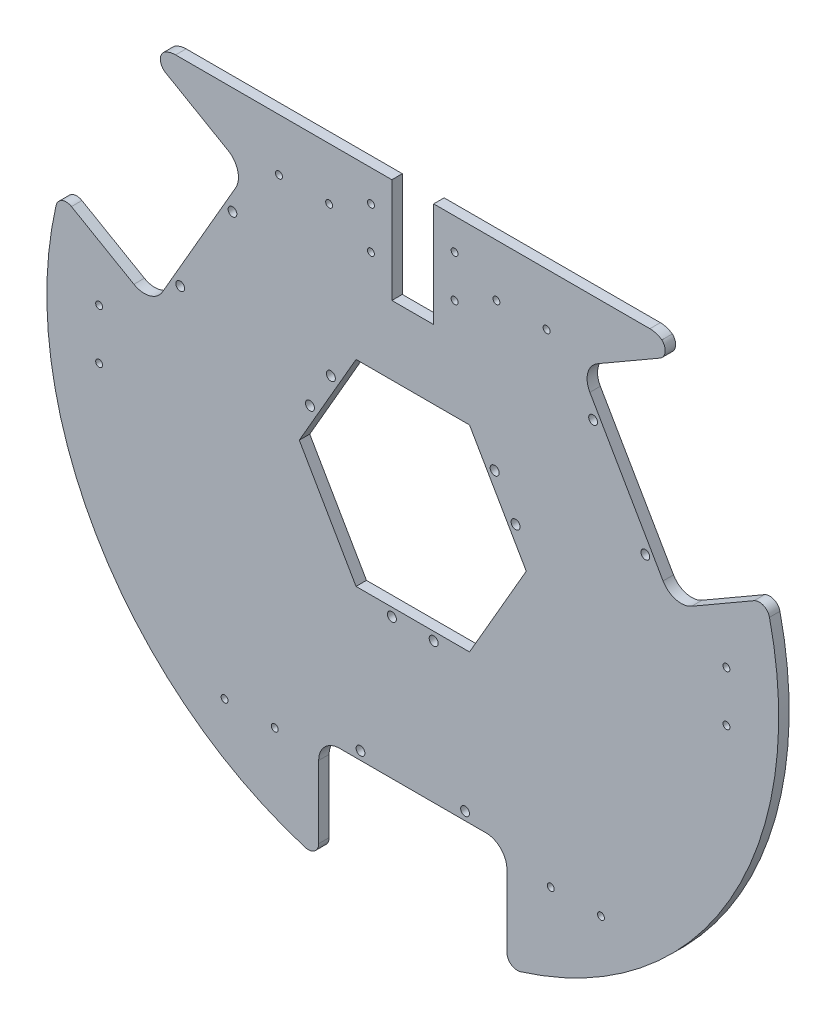
SolidWorks part; units mm, degrees
material "AISI 304"
ref_plane "前基準面" through (0, 0, 0) normal (0, 0, 1) x (1, 0, 0)
ref_plane "上基準面" through (0, 0, 0) normal (0, 1, 0) x (1, 0, 0)
ref_plane "右基準面" through (0, 0, 0) normal (1, 0, 0) x (0, 0, -1)
ref_axis "基準軸1" through (0, 0, -0.25) along (0, 0, 1)
sketch "草圖1" plane through (0, 0, 0) normal (0, 0, 1) x (1, 0, 0)
  circle A1 centre (0, 0) radius 175
  dimension "D1" = 350
extrude "填料-伸長1" add sketch "草圖1" along normal blind 5
sketch "草圖6" plane through (0, 0, 5) normal (0, 0, 1) x (1, 0, 0)
  line L10 (0, 0) -> (0, -143.5577) construction
  line L13 (-45, -169.1153) -> (-45, -118)
  line L14 (-45, -118) -> (45, -118)
  line L15 (45, -169.1153) -> (45, -118)
  line L16 (-45, -169.1153) -> (45, -118) construction
  line L17 (-45, -118) -> (45, -169.1153) construction
  arc A0 (-45, -169.1153) -> (45, -169.1153) centre (0, 0) ccw
  circle A1 centre (0, 0) radius 175 construction
  dimension "D1" = 118
  dimension "D2" = 90
extrude "除料-伸長1" cut sketch "草圖6" against normal through all
sketch "草圖12" plane through (0, 0, 5) normal (0, 0, 1) x (1, 0, 0)
  line L0 (-117.1537, 130) -> (117.1537, 130)
  arc A0 (45, -169.1153) -> (-45, -169.1153) centre (0, 0) ccw construction
  arc A1 (-117.1537, 130) -> (117.1537, 130) centre (0, 0) cw
  arc A2 (45, -169.1153) -> (-45, -169.1153) centre (0, 0) ccw construction
  dimension "D1" = 130
extrude "除料-伸長3" cut sketch "草圖12" against normal through all
hole_wizard "M5x0.8 螺紋孔1" positions "草圖4" profile "草圖5" tap size "M5x0.8" standard "Ansi Metric" end condition through all
sketch "草圖4" plane through (0, 0, 5) normal (0, 0, 1) x (1, 0, 0)
  line L0 (0, -118) -> (0, -114) construction
  line L4 (-25, -114) -> (25, -114) construction
  line L6 (45, -118) -> (-45, -118) construction
  point P10 (-25, -114)
  point P11 (25, -114)
  dimension "D1" = 4
  dimension "D2" = 50
sketch "草圖5" plane through (25, -114, 5) normal (1, 0, 0) x (0, -1, 0)
  line L0 (0, 0) -> (0, 5)
  line L1 (0, 5) -> (2.1, 5)
  line L2 (2.1, 5) -> (2.1, 0)
  line L5 (2.1, 0) -> (0, 0)
  line L11 (0, -6.35) -> (0, 107.95) construction
  dimension "貫穿螺孔鑽直徑" = 4.2
  dimension "貫穿螺孔鑽深度" = 5
hole_wizard "M4 餘隙孔1" positions "草圖9" profile "草圖10" hole size "M4" standard "Ansi Metric" end condition through all
sketch "草圖9" plane through (0, 0, 5) normal (0, 0, 1) x (1, 0, 0)
  line L0 (-25, -114) -> (25, -114) construction
  line L3 (0, -114) -> (0, -51) construction
  line L6 (-10, -51) -> (10, -51) construction
  point P14 (-10, -51)
  point P15 (10, -51)
  dimension "D1" = 20
  dimension "D2" = 63
sketch "草圖10" plane through (10, -51, 5) normal (1, 0, 0) x (0, -1, 0)
  line L0 (0, 0) -> (0, 5)
  line L1 (0, 5) -> (2.15, 5)
  line L2 (2.15, 5) -> (2.15, 0)
  line L5 (2.15, 0) -> (0, 0)
  line L11 (0, -6.35) -> (0, 107.95) construction
  dimension "貫穿孔直徑" = 4.3
  dimension "貫穿孔深度" = 5
fillet "圓角1" radius 10 2 edges at (-45, -118, 2.5) (45, -118, 2.5)
fillet "圓角2" radius 5 2 edges at (45, -169.1153, 2.5) (-45, -169.1153, 2.5)
pattern_circular "環狀複製排列1" count 3 over 360 about axis through (0, 0, -0.25) along (0, 0, 1) of "M5x0.8 螺紋孔1", "除料-伸長1", "M4 餘隙孔1", "圓角1", "圓角2"
sketch "草圖11" plane through (0, 0, 5) normal (0, 0, 1) x (1, 0, 0)
  line L7 (54.2709, 0) -> (27.1355, 47)
  line L8 (27.1355, 47) -> (-27.1355, 47)
  line L9 (-27.1355, 47) -> (-54.2709, 0)
  line L10 (-54.2709, 0) -> (-27.1355, -47)
  line L11 (-27.1355, -47) -> (27.1355, -47)
  line L12 (27.1355, -47) -> (54.2709, 0)
  circle A1 centre (0, 0) radius 47 construction
  dimension "D1" = 94
extrude "除料-伸長2" cut sketch "草圖11" against normal through all
hole_wizard "M4x0.7 螺紋孔1" positions "草圖17" profile "草圖18" tap size "M4x0.7" standard "Ansi Metric" end condition through all
sketch "草圖17" plane through (0, 0, 0) normal (0, 0, 1) x (1, 0, 0)
  line L0 (0, 0) -> (0, 130) construction
  line L1 (-117.1537, 130) -> (117.1537, 130) construction
  line L2 (-40, 105) -> (-64, 105) construction
  line L5 (40, 105) -> (64, 105) construction
  point P7 (-40, 105)
  point P10 (40, 105)
  point P13 (-64, 105)
  point P18 (64, 105)
  dimension "D1" = 40
  dimension "D2" = 105
  dimension "D3" = 24
sketch "草圖18" plane through (64, 105, 0) normal (1, 0, 0) x (0, 1, 0)
  line L0 (0, 0) -> (0, 5)
  line L1 (0, 5) -> (1.65, 5)
  line L2 (1.65, 5) -> (1.65, 0)
  line L5 (1.65, 0) -> (0, 0)
  line L11 (0, -6.35) -> (0, 107.95) construction
  dimension "貫穿螺孔鑽直徑" = 3.3
  dimension "貫穿螺孔鑽深度" = 5
hole_wizard "M4x0.7 螺紋孔2" positions "草圖21" profile "草圖22" tap size "M4x0.7" standard "Ansi Metric" end condition through all
sketch "草圖21" plane through (0, 0, 0) normal (0, 0, -1) x (-1, 0, 0)
  line L0 (0, 0) -> (-175, 0) construction
  arc A0 (-170.5864, 39.055) -> (-51.4706, -167.2596) centre (0, 0) ccw construction
  point P9 (-150, 8)
  point P11 (-150, -16)
  dimension "D1" = 24
  dimension "D2" = 150
  dimension "D3" = 16
sketch "草圖22" plane through (150, -16, 0) normal (1, 0, 0) x (0, 1, 0)
  line L0 (0, 0) -> (0, 5)
  line L1 (0, 5) -> (1.65, 5)
  line L2 (1.65, 5) -> (1.65, 0)
  line L5 (1.65, 0) -> (0, 0)
  line L11 (0, -6.35) -> (0, 107.95) construction
  dimension "貫穿螺孔鑽直徑" = 3.3
  dimension "貫穿螺孔鑽深度" = 5
mirror "鏡射1" about plane through (0, 0, 0) normal (1, 0, 0) of "M4x0.7 螺紋孔2"
hole_wizard "M4x0.7 螺紋孔3" positions "草圖23" profile "草圖25" tap size "M4x0.7" standard "Ansi Metric" end condition through all
sketch "草圖23" plane through (0, 0, 0) normal (0, 0, -1) x (-1, 0, 0)
  line L0 (-90, -125) -> (90, -125) construction
  line L3 (0, -125) -> (0, 0) construction
  point P0 (-90, -125)
  point P1 (90, -125)
  point P12 (-66, -125)
  point P14 (66, -125)
  dimension "D1" = 180
  dimension "D2" = 125
  dimension "D3" = 24
  dimension "D4" = 24
sketch "草圖25" plane through (90, -125, 0) normal (1, 0, 0) x (0, 1, 0)
  line L0 (0, 0) -> (0, 5)
  line L1 (0, 5) -> (1.65, 5)
  line L2 (1.65, 5) -> (1.65, 0)
  line L5 (1.65, 0) -> (0, 0)
  line L11 (0, -6.35) -> (0, 107.95) construction
  dimension "貫穿螺孔鑽直徑" = 3.3
  dimension "貫穿螺孔鑽深度" = 5
hole_wizard "M4x0.7 螺紋孔4" positions "草圖28" profile "草圖29" tap size "M4x0.7" standard "Ansi Metric" end condition through all
sketch "草圖28" plane through (0, 0, 0) normal (0, 0, -1) x (-1, 0, 0)
  line L0 (0, 0) -> (0, 95) construction
  line L1 (20, 95) -> (-20, 95) construction
  point P1 (0, 95)
  point P9 (20, 95)
  point P10 (-20, 95)
  dimension "D1" = 95
  dimension "D2" = 40
sketch "草圖29" plane through (20, 95, 0) normal (1, 0, 0) x (0, 1, 0)
  line L0 (0, 0) -> (0, 5)
  line L1 (0, 5) -> (1.65, 5)
  line L2 (1.65, 5) -> (1.65, 0)
  line L5 (1.65, 0) -> (0, 0)
  line L11 (0, -6.35) -> (0, 107.95) construction
  dimension "貫穿螺孔鑽直徑" = 3.3
  dimension "貫穿螺孔鑽深度" = 5
pattern_linear "直線複製排列1" count 2 spacing 20 along (0, 1, 0) of "M4x0.7 螺紋孔4"
sketch "草圖30" plane through (0, 0, 0) normal (0, 0, -1) x (-1, 0, 0)
  line L0 (117.1537, 130) -> (-117.1537, 130) construction
  line L1 (10, 130) -> (-10, 130)
  line L2 (10, 130) -> (10, 80)
  line L3 (10, 80) -> (-10, 80)
  line L4 (-10, 130) -> (-10, 80)
  point P6 (0, 130)
  dimension "D1" = 20
  dimension "D2" = 50
extrude "除料-伸長4" cut sketch "草圖30" against normal through all
fillet "圓角3" radius 10 2 edges at (117.1537, 130, 2.5) (-117.1537, 130, 2.5)
